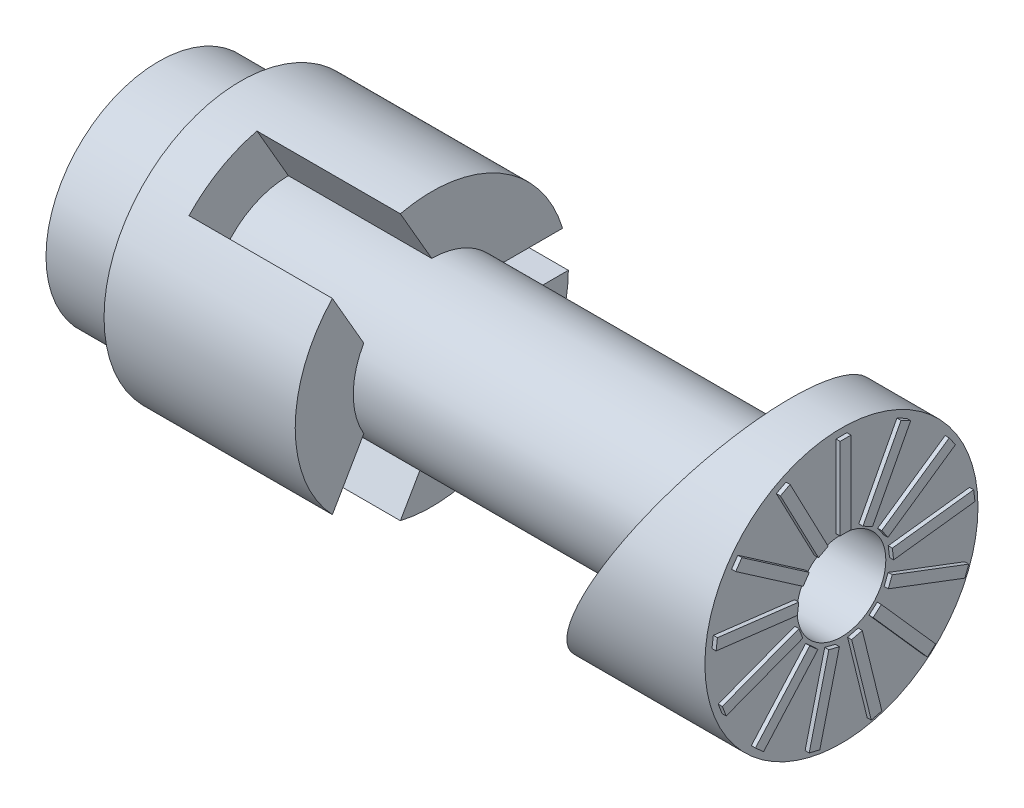
SolidWorks part; units mm, degrees
ref_plane "前视基准面" through (0, 0, 0) normal (0, 0, 1) x (1, 0, 0)
ref_plane "上视基准面" through (0, 0, 0) normal (0, 1, 0) x (1, 0, 0)
ref_plane "右视基准面" through (0, 0, 0) normal (1, 0, 0) x (0, 0, -1)
other "Configuration Table"
sketch "草图1" plane through (0, 0, 0) normal (0, 0, 1) x (1, 0, 0)
  line L0 (0, 0) -> (50, 0) construction
  line L1 (50, 0) -> (50, -10)
  line L2 (50, -10) -> (36, -10)
  line L3 (36, -10) -> (36, -5.75)
  line L4 (36, -5.75) -> (20, -5.75)
  line L5 (20, -5.75) -> (20, -10)
  line L6 (20, -10) -> (6, -10)
  line L7 (6, -10) -> (6, -8.25)
  line L8 (6, -8.25) -> (0, -8.25)
  line L9 (0, -8.25) -> (0, 0)
  line L10 (36, -5.75) -> (36, 0)
  dimension "D1" = 50
  dimension "D2" = 16.5
  dimension "D3" = 6
  dimension "D4" = 14
  dimension "D5" = 20
  dimension "D6" = 11.5
  dimension "D7" = 30
revolve "旋转1" add sketch "草图1" angle 360 about L0 region at (16.1439, -4.1516, 0)
sketch "草图2" plane through (20, 0, 0) normal (1, 0, 0) x (0, 0, -1)
  line L0 (0, 0) -> (10, 0) construction
  line L1 (4.9796, 2.875) -> (9.5778, 2.875)
  line L2 (4.9796, -2.875) -> (9.5778, -2.875)
  line L3 (0, -5.75) -> (-2.2991, -9.7321)
  line L4 (-4.9796, -2.875) -> (-7.2787, -6.8571)
  line L5 (-4.9796, 2.875) -> (-7.2787, 6.8571)
  line L6 (0, 5.75) -> (-2.2991, 9.7321)
  circle A0 centre (0, 0) radius 10 construction
  circle A1 centre (0, 0) radius 5.75 construction
  circle A2 centre (0, 0) radius 10
  circle A3 centre (0, 0) radius 5.75
  point P11 (0, 0)
  point P20 (0, 0)
  circle M6 centre (0, 0) radius 10
  circle M7 centre (0, 0) radius 5.75
  dimension "D1" = 5.75
  dimension "D2" = 3
extrude "切除-拉伸1" cut sketch "草图2" against normal blind 10.5 contours L6 L5 M7 M6 | L0 A2 L1 M7 | L4 L3 M7 M6 region at (20, 1.4561, -7.6764) region at (20, 6.6479, 3.8382) region at (20, -6.6479, 3.8382)
revolve "旋转2" add sketch "草图1<3>" angle 360 about L0 region at (43, -5, 0)
sketch "草图1<3>" plane through (0, 0, 0) normal (0, 0, 1) x (1, 0, 0) same geometry as "草图1"
sketch "草图3" plane through (0, 0, 0) normal (0, 0, 1) x (1, 0, 0)
  line L0 (36, -10) -> (36, 10)
  line L1 (36, 10) -> (46.25, 10)
  line L2 (50, 10) -> (36, 10) construction
  line L3 (46.25, 10) -> (36, -10)
  line L4 (50, -10) -> (50, 10) construction
  dimension "D1" = 3.75
extrude "切除-拉伸2" cut sketch "草图3" against normal through all both and the other way through all
sketch "草图4" plane through (36, 0, 0) normal (1, 0, 0) x (0, 0, -1)
  circle A1 centre (0, 0) radius 5.75
  circle A2 centre (0, 0) radius 5.75
  dimension "D1" = 0
extrude "凸台-拉伸1" add sketch "草图4" along normal up to next
sketch "草图5" plane through (50, 0, 0) normal (1, 0, 0) x (0, 0, -1)
  circle A0 centre (0, 0) radius 3.25
  dimension "D1" = 6.5
extrude "切除-拉伸3" cut sketch "草图5" against normal through all and the other way through all
sketch "草图6" plane through (50, 0, 0) normal (1, 0, 0) x (0, 0, -1)
  line L1 (-0.4, 9.5) -> (0.4, 9.5)
  line L2 (-0.4, 9.5) -> (-0.4, 3.5)
  line L3 (-0.4, 3.5) -> (0.4, 3.5)
  line L4 (0.4, 9.5) -> (0.4, 3.5)
  line L5 (-0.4, 9.5) -> (0.4, 3.5) construction
  line L6 (-0.4, 3.5) -> (0.4, 9.5) construction
  point P0 (0, 6.5)
  point P5 (0, 0)
  dimension "D1" = 6
  dimension "D2" = 0.8
  dimension "D3" = 3.5
extrude "凸台-拉伸2" add sketch "草图6" along normal blind 0.3
pattern_circular "阵列(圆周)1" count 13 over 360 about axis through (50, 0, 0) along (-1, 0, 0) of "凸台-拉伸2"
